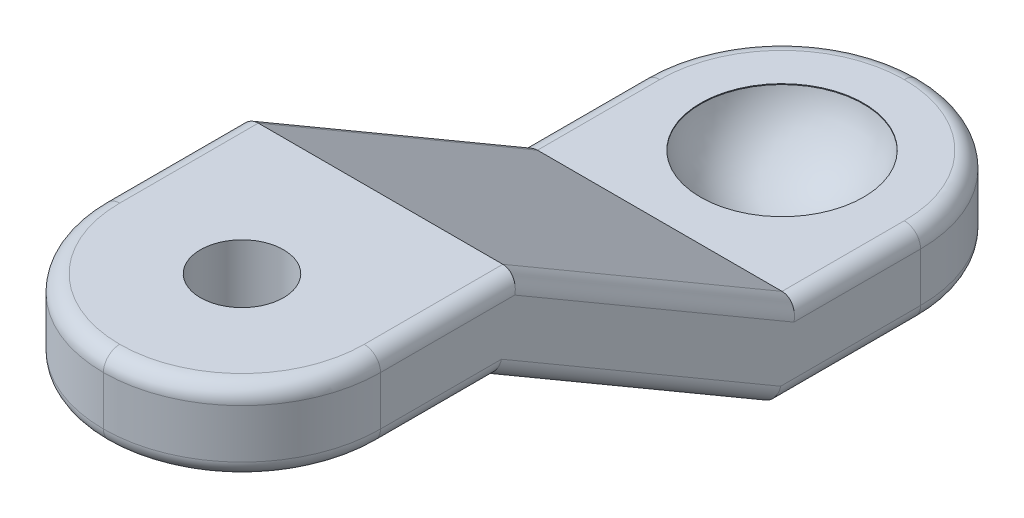
SolidWorks part; units mm, degrees
ref_plane "Front Plane" through (0, 0, 0) normal (0, 0, 1) x (1, 0, 0)
ref_plane "Top Plane" through (0, 0, 0) normal (0, 1, 0) x (1, 0, 0)
ref_plane "Right Plane" through (0, 0, 0) normal (1, 0, 0) x (0, 0, -1)
sketch "ProfileSketch1" plane through (0, 0, 0) normal (1, 0, 0) x (0, 0, -1)
  line L0 (0, 0) -> (34, 0)
  line L1 (34, 0) -> (68.2531, -20)
  line L2 (68.2531, -20) -> (100.2531, -20)
  line L3 (17, 0) -> (17, 2.8642) construction
  line L4 (84.2531, -20) -> (84.2531, 2.8642) construction
  dimension "D1" = 34
  dimension "D2" = 20
  dimension "D4" = 32
  dimension "D3" = 67.2531
extrude "ProfileExtrude-Thin1" add sketch "ProfileSketch1" along normal blind 34 thin thin type one direction wall 10
fillet "Fillet1" radius 17 1 edges at (34, -5, 0)
fillet "Fillet2" radius 17 1 edges at (0, -5, 0)
sketch "FlangeNutHoleSketch4" plane through (0, 0, 0) normal (0, 1, 0) x (1, 0, 0)
  line L0 (0, 17) -> (0, 34) construction
  line L1 (34, 34) -> (0, 34) construction
  circle A0 centre (17, 17) radius 5.1
  dimension "D1" = 17
  dimension "D3" = 10.2
  dimension "D2" = 17
extrude "FlangeNutHoleCut-Extrude5" cut sketch "FlangeNutHoleSketch4" against normal through all
sketch "DomeIndentSketch6" plane through (0, -20, 0) normal (0, 1, 0) x (1, 0, 0)
  line L4 (0, 68.2531) -> (0, 100.2531) construction
  line L5 (34, 100.2531) -> (0, 100.2531) construction
  circle A0 centre (17, 83.2531) radius 10
  dimension "D2" = 17
  dimension "D1" = 20
  dimension "D3" = 17
extrude "DomeIndentCut-Extrude8" cut sketch "DomeIndentSketch6" against normal blind 0.1
dome "Dome2" faces to dome 1 distance 8 reverse direction yes elliptical dome no face at (17, -20.1, -73.2531) parameters "D1"=8
fillet "Fillet3" radius 17 1 edges at (34, -25, -100.2531)
fillet "Fillet4" radius 17 1 edges at (0, -25, -100.2531)
sketch "FlangeNutHolesSketch2" plane through (0, -10, 0) normal (0, -1, 0) x (1, 0, 0)
  circle A0 centre (9, -9) radius 2
  circle A1 centre (25, -9) radius 2
  circle A2 centre (25, -25) radius 2
  circle A3 centre (9, -25) radius 2
  dimension "D5" = 4
  dimension "D1" = 8
  dimension "D2" = 16
  dimension "D3" = 8
  dimension "D4" = 16
fillet "BottomBoundaryFillet5" radius 2 10 edges at (0, -20, -48.4208) (0, -30, -74.4003) (4.9792, -30, -95.2739) (29.0208, -30, -95.2739) (34, -30, -74.4003) (34, -20, -48.4208) (34, -10, -24.1471) (29.0208, -10, -4.9792) (4.9792, -10, -4.9792) (0, -10, -24.1471)
fillet "Fillet6" radius 2 10 edges at (34, -10, -51.1266) (34, 0, -25.5) (29.0208, 0, -4.9792) (4.9792, 0, -4.9792) (0, 0, -25.5) (0, -10, -51.1266) (0, -20, -75.7531) (4.9792, -20, -95.2739) (34, -20, -75.7531) (29.0208, -20, -95.2739)
extrude "Cut-Extrude1" cut sketch "FlangeNutHolesSketch2" against normal blind 4
equation "\"D1@ProfileSketch1\"=\"BedSupportLeadScrewPadSize\""
equation "\"StandardWallThickness\"= 3mm"
equation "\"BedToBuildPlateStandoffPadSize\"= 10mm"
equation "\"BuildPlateStandoffHolesDistanceFromLeftOrRight\"= 7mm"
equation "\"BuildPlateStandoffHolesDistanceFromFrontOrBack\"= 41mm"
equation "\"DistanceFromBuildPlateSideToStepperHole\"= ( \"DistanceBetweenLeftToRightStepperHoles\" - \"BuildPlateWidth\" ) / 2'Equals 55.825"
equation "\"DistanceBetweenLeftToRightStepperHoles\"= \"FrontBackRailLength\" - \"StepperMountingHoleOffsetFromLeftOrRightSide\" * 2 - \"StepperMountingHoleDistance\"'Equals 461.65"
equation "\"FrontBackRailLength\"= 510mm"
equation "\"StepperMountingHoleOffsetFromLeftOrRightSide\"= \"StepperMountingHoleOffsetFromItsSide\" + \"RailThickness\""
equation "\"StepperMountingHoleDistance\"= 31mm'Spec"
equation "\"StepperMountingHoleOffsetFromItsSide\"= 5.5mm'Spec"
equation "\"RailThickness\"= .125in'Spec"
equation "\"LeadScrewNutPadSize\"= \"LeadScrewNutMountingHoleFlangeDiameter\" + 2mm'Equals 24"
equation "\"LeadScrewNutInnerShaftFlangeDiameter\"= 10.2mm'Spec"
equation "\"LeadScrewNutMountHoleDiameter\"= \"M3HeatInsertHoleDiameter\""
equation "\"LeadScrewNutMountingHoleFlangeDiameter\"= 22mm'Spec"
equation "\"LeadScrewNutMountingHoleDistance\"= 16mm'Spec"
equation "\"M3HeatInsertHoleDiameter\"= 4mm'Spec"
equation "\"D1@Fillet1\"=\"BedSupportLeadScrewPadSize\"/2"
equation "\"D1@Fillet2\"=\"BedSupportLeadScrewPadSize\"/2"
equation "\"D1@FlangeNutHoleSketch4\"=\"BedSupportLeadScrewPadSize\"  / 2"
equation "\"D2@FlangeNutHoleSketch4\"=\"BedSupportLeadScrewPadSize\" / 2"
equation "\"D3@FlangeNutHoleSketch4\" = \"LeadScrewNutInnerShaftFlangeDiameter\""
equation "\"D2@DomeIndentSketch6\" = \"BedSupportLeadScrewPadSize\" / 2"
equation "\"D3@DomeIndentSketch6\" = \"BedSupportLeadScrewPadSize\" / 2"
equation "\"BedSpringHoleSize\"= 3mm"
equation "\"BuildPlateWidth\"= 350mm'Spec"
equation "\"BuildPlateLength\"= 350mm'Spec"
equation "\"BuildPlateBoreDiameter\"= 5mm'Spec"
equation "\"BuildPlateBoreDepth\"= 3mm'Spec"
equation "\"BuildPlateDepth\"= 8mm'Spec"
equation "\"BuildPlateFlankingHoles\"= 38mm"
equation "\"BuildPlateStandoffHolesDistanceFromFront\"= 7mm"
equation "\"BedSupportLeadScrewPadSize\"= \"LeadScrewNutPadSize\" + 10mm"
equation "\"D1@ProfileExtrude-Thin1\"=\"BedSupportLeadScrewPadSize\""
equation "\"BuildPlateBallDiameter\"= 12mm"
equation "\"BedSupportBuildPlatePadSize\"= \"BuildPlateBallDiameter\" + 20mm"
equation "\"D4@ProfileSketch1\"=\"BedSupportBuildPlatePadSize\""
equation "\"D3@ProfileSketch1\" = \"HypotonusOfStepperAndBuildPlateHoles\""
equation "\"D1@Fillet3\"=\"BedSupportLeadScrewPadSize\"/2"
equation "\"D1@Fillet4\"=\"BedSupportLeadScrewPadSize\"/2"
equation "\"HypotonusOfStepperAndBuildPlateHoles\"= sqr ( ( \"DistanceFromBuildPlateSideToStepperHole\" + \"BuildPlateStandoffHolesDistanceFromLeftOrRight\" ) ^ 2 + ( \"BuildPlateStandoffHolesDistanceFromFrontOrBack\" - \"BedSupportLeadScrewPadSize\" / 2 ) ^ 2 )"
equation "\"D1@FlangeNutHolesSketch2\" = \"LeadScrewNutMountingHoleDistance\" / 2"
equation "\"D2@FlangeNutHolesSketch2\" = \"LeadScrewNutMountingHoleDistance\""
equation "\"D3@FlangeNutHolesSketch2\" = \"LeadScrewNutMountingHoleDistance\" / 2"
equation "\"D4@FlangeNutHolesSketch2\" = \"LeadScrewNutMountingHoleDistance\""
equation "\"D5@FlangeNutHolesSketch2\" = \"M3HeatInsertHoleDiameter\""
equation "\"D1@Cut-Extrude1\"=\"M3HeatInsertHoleDiameter\""
